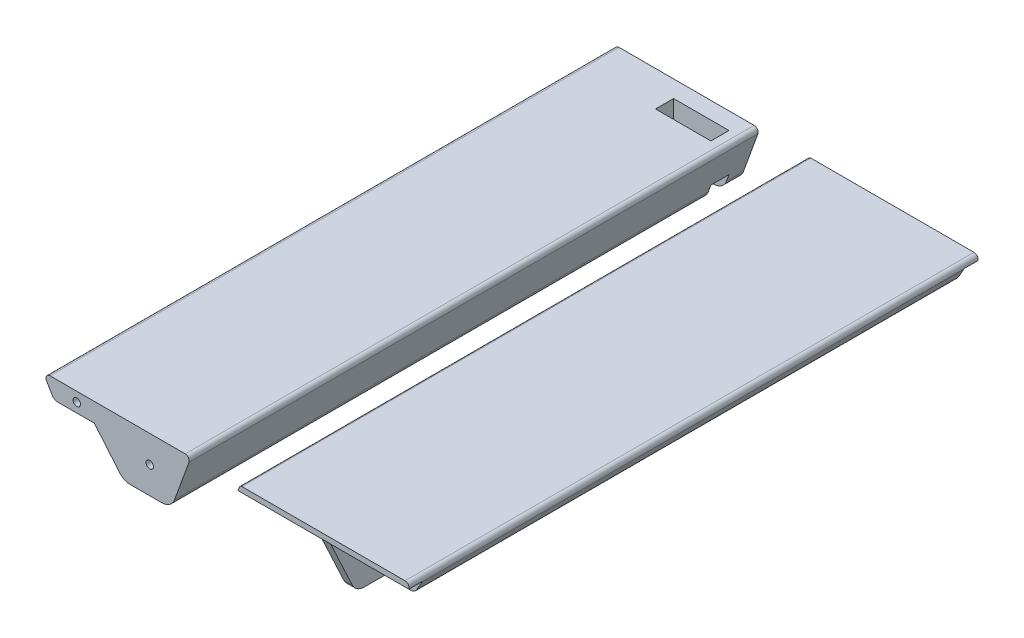
SolidWorks part; units mm, degrees
ref_plane "Front plane" through (0, 0, 0) normal (0, 0, 1) x (1, 0, 0)
ref_plane "Top plane" through (0, 0, 0) normal (0, 1, 0) x (1, 0, 0)
ref_plane "Right Plane" through (0, 0, 0) normal (1, 0, 0) x (0, 0, -1)
sketch "Sketch1" plane through (0, 0, 0) normal (0, 0, 1) x (1, 0, 0)
  line L0 (0, 0) -> (50, 0)
  line L1 (51.4095, -2.013) -> (44.8628, -20)
  line L2 (44.8628, -20) -> (27.295, -20)
  line L3 (27.295, -20) -> (16.3868, -7)
  line L5 (-1.299, -2.25) -> (0.7217, -5.75)
  line L6 (2.8868, -7) -> (16.3868, -7)
  line L8 (71, 0) -> (131.3335, 0)
  line L9 (132.6325, -2.25) -> (130.6118, -5.75)
  line L10 (100.6668, -2) -> (69.5719, -2)
  line L11 (100.6668, -2) -> (100.6668, -22)
  line L12 (100.6668, -22) -> (103.8168, -22)
  line L13 (70.0603, -0.658) -> (69.5719, -2)
  line L14 (103.8168, -22) -> (103.8168, -2)
  line L15 (103.8168, -2) -> (122.8168, -2)
  line L16 (122.8168, -2) -> (122.8168, -7)
  line L17 (122.8168, -7) -> (128.4468, -7)
  line L19 (123.8168, -2) -> (129.8168, -2)
  line L20 (123.8168, -2) -> (123.8168, -4.5)
  line L21 (123.8168, -4.5) -> (129.8168, -4.5)
  line L22 (129.8168, -2) -> (129.8168, -4.5)
  arc A0 (50, 0) -> (51.4095, -2.013) centre (50, -1.5) cw
  arc A1 (-1.299, -2.25) -> (0, 0) centre (0, -1.5) cw
  arc A2 (0.7217, -5.75) -> (2.8868, -7) centre (2.8868, -4.5) ccw
  arc A4 (131.3335, 0) -> (132.6325, -2.25) centre (131.3335, -1.5) cw
  arc A7 (128.4468, -7) -> (130.6118, -5.75) centre (128.4468, -4.5) ccw
  arc A8 (71, 0) -> (70.0603, -0.658) centre (71, -1) ccw
  dimension "D2" = 1.5
  dimension "D8" = 2.5
  dimension "D10" = 21
  dimension "D12" = 2.5
  dimension "D14" = 125.56
  dimension "D15" = 27.78
  dimension "D1" = 20
  dimension "D3" = 50
  dimension "D4" = 60
  dimension "D5" = 70
  dimension "D6" = 13.5
  dimension "D7" = 7
  dimension "D9" = 60
  dimension "D11" = 60
  dimension "D13" = 2
  dimension "D16" = 3.15
  dimension "D17" = 20
  dimension "D18" = 19
  dimension "D19" = 6
  dimension "D20" = 2.5
  dimension "D21" = 1
extrude "Boss-Extrude1" add sketch "Sketch1" along normal blind 105.25
sketch "Sketch2" plane through (0, 0, 105.25) normal (0, 0, 1) x (1, 0, 0)
  line L0 (9.8868, 0) -> (9.8868, -7) construction
  line L1 (50, 0) -> (0, 0) construction
  line L2 (2.8868, -7) -> (16.3868, -7) construction
  circle A0 centre (9.8868, -3.5) radius 1.375
  arc A1 (0.7217, -5.75) -> (2.8868, -7) centre (2.8868, -4.5) ccw construction
  circle A2 centre (36.8868, -10) radius 1.375
  dimension "D1" = 2.75
  dimension "D2" = 7
  dimension "D3" = 10
  dimension "D4" = 27
extrude "Cut-Extrude1" cut sketch "Sketch2" against normal blind 15
sketch "Sketch3" plane through (0, 0, 105.25) normal (0, 0, 1) x (1, 0, 0)
  line L0 (122.8168, -2) -> (132.7477, -2)
  line L1 (122.8168, -2) -> (122.8168, -7) construction
  line L2 (122.8168, -7) -> (128.4468, -7) construction
  line L3 (130.6118, -5.75) -> (132.6325, -2.25) construction
  line L4 (122.8168, -2) -> (122.8168, -7)
  line L5 (122.8168, -7) -> (128.4468, -7)
  line L6 (130.6118, -5.75) -> (132.6325, -2.25)
  arc A0 (128.4468, -7) -> (130.6118, -5.75) centre (128.4468, -4.5) ccw construction
  arc A1 (132.6325, -2.25) -> (131.3335, 0) centre (131.3335, -1.5) ccw construction
  arc A2 (128.4468, -7) -> (130.6118, -5.75) centre (128.4468, -4.5) ccw
  arc A3 (132.6325, -2.25) -> (132.7477, -2) centre (131.3335, -1.5) ccw
extrude "Cut-Extrude2" cut sketch "Sketch3" against normal blind 5
mirror "Mirror1" about plane through (0, -1.5, 0) normal (0, 0, -1) of bodies 104 107 103
fillet "Fillet1" radius 5 2 edges at (44.8628, -20, 0) (27.295, -20, 0)
sketch "Sketch4" plane through (103.8168, 0, 0) normal (1, 0, 0) x (0, 0, -1)
  line L0 (-105.25, -22) -> (-105.25, -2)
  line L1 (-105.25, -2) -> (-95.9238, -22)
  line L2 (-105.25, -22) -> (105.25, -22) construction
  line L3 (-95.9238, -22) -> (-105.25, -22)
  line L4 (105.25, -2) -> (90.25, -2)
  line L5 (-105.25, -2) -> (105.25, -2) construction
  line L6 (90.25, -2) -> (80.9238, -22)
  line L7 (80.9238, -22) -> (105.25, -22)
  line L8 (105.25, -22) -> (105.25, -2)
  line L9 (-100.25, -2) -> (-105.25, -2) construction
  circle A0 centre (-81.25, -17) radius 1.375
  circle A1 centre (-61.25, -17) radius 1.375
  circle A2 centre (-41.25, -17) radius 1.375
  circle A3 centre (-21.25, -17) radius 1.375
  circle A4 centre (-1.25, -17) radius 1.375
  circle A5 centre (18.75, -17) radius 1.375
  circle A6 centre (38.75, -17) radius 1.375
  circle A7 centre (58.75, -17) radius 1.375
  circle A8 centre (78.75, -17) radius 1.375
  dimension "D5" = 2.75
  dimension "D8" = 20
  dimension "D1" = 25
  dimension "D2" = 25
  dimension "D3" = 15
  dimension "D4" = 24
  dimension "D6" = 15
  dimension "D7" = 9
extrude "Cut-Extrude3" cut sketch "Sketch4" against normal up to vertex (3.15 mm away) up to point (100.6668, -22, -105.25)
fillet "Fillet2" radius 5 2 edges at (102.2418, -22, 95.9238) (102.2418, -22, -80.9238)
sketch "Sketch5" plane through (0, 0, 0) normal (0, 1, 0) x (1, 0, 0)
  line L0 (50, 105.25) -> (0, 105.25) construction
  line L1 (47, 98.95) -> (26.5, 98.95)
  line L2 (47, 98.95) -> (47, 92.25)
  line L3 (47, 92.25) -> (26.5, 92.25)
  line L4 (26.5, 98.95) -> (26.5, 92.25)
  dimension "D1" = 20.5
  dimension "D2" = 6.7
  dimension "D3" = 13
  dimension "D4" = 47
extrude "Cut-Extrude4" cut sketch "Sketch5" against normal through all
sketch "Sketch6" plane through (0, 0, -105.25) normal (0, 0, -1) x (-1, 0, 0)
  line L0 (-41.5, -11.2) -> (-32, -11.2) construction
  line L1 (-26.5, 0) -> (-47, 0) construction
  line L2 (-50, 0) -> (0, 0) construction
  circle A0 centre (-41.5, -11.2) radius 1.125
  circle A1 centre (-32, -11.2) radius 1.125
  point P4 (-36.75, 0)
  point P5 (-36.75, -11.2)
  dimension "D3" = 2.25
  dimension "D1" = 11.2
  dimension "D2" = 9.5
extrude "Cut-Extrude5" cut sketch "Sketch6" against normal blind 20
sketch "Sketch7" plane through (0, 0, -105.25) normal (0, 0, -1) x (-1, 0, 0)
  circle A0 centre (-41.5, -11.2) radius 2.5
  circle A1 centre (-32, -11.2) radius 2.5
  dimension "D1" = 5
extrude "Cut-Extrude6" cut sketch "Sketch7" against normal up to vertex (13 mm away) up to point (26.5, 0, -92.25)
